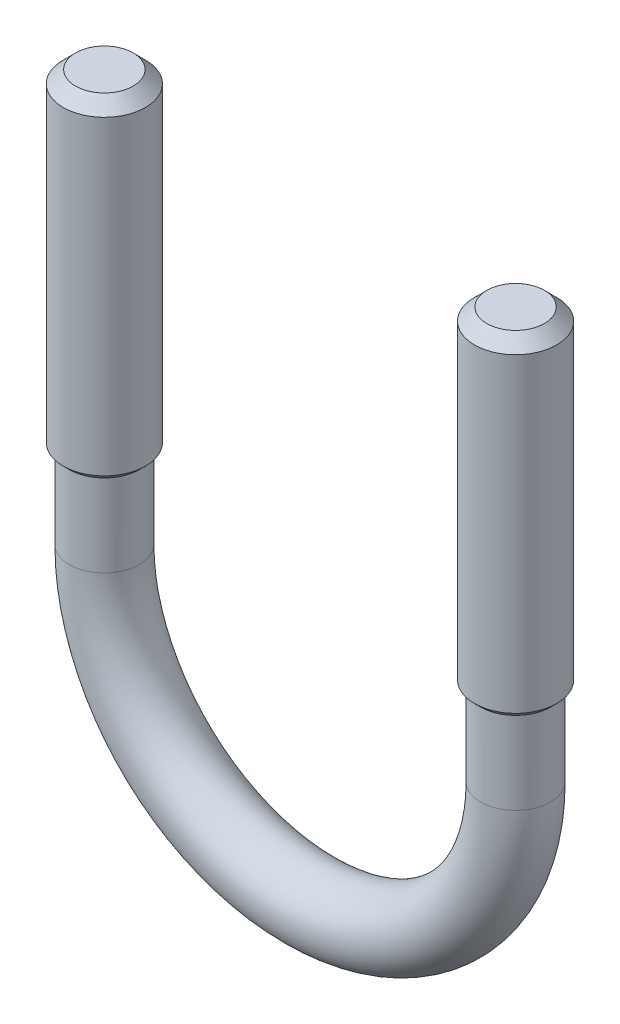
SolidWorks part; units mm, degrees
material "6061-T6 (SS)"
ref_plane "Front" through (0, 0, 0) normal (0, 0, 1) x (1, 0, 0)
ref_plane "Top" through (0, 0, 0) normal (0, 1, 0) x (1, 0, 0)
ref_plane "Right" through (0, 0, 0) normal (1, 0, 0) x (0, 0, -1)
sketch "Sketch1" plane through (0, 0, 0) normal (0, 0, 1) x (1, 0, 0)
  line L0 (-12.7, 31.75) -> (-19.05, 31.75) construction
  line L1 (-15.875, 31.75) -> (-15.875, 0) construction
  line L2 (0, -13.1699) -> (0, -18.5801)
  line L3 (15.875, 0) -> (15.875, 31.75) construction
  line L4 (19.05, 31.75) -> (12.7, 31.75) construction
  line L5 (-12.7, 6.35) -> (-19.05, 6.35)
  line L6 (0, -12.7) -> (0, -19.05) construction
  line L7 (-12.7, 31.75) -> (-12.7, 6.35)
  line L8 (-12.5625, 32.9406) -> (-12.5625, 31.6706) construction
  line L9 (-12.5625, 31.6706) -> (-13.6624, 32.3056) construction
  line L10 (-13.6624, 32.3056) -> (-12.5625, 32.9406) construction
  line L11 (-12.5625, 32.3056) -> (-12.7, 32.3056) construction
  line L12 (-13.6624, 32.3056) -> (-13.5249, 32.3056) construction
  line L13 (-12.7, 32.8612) -> (-12.7, 31.75) construction
  line L14 (-13.5249, 32.385) -> (-13.5249, 32.2262)
  line L15 (-12.6313, 32.9009) -> (-12.6313, 31.7103)
  line L16 (-12.6313, 31.7103) -> (-13.5249, 32.2262)
  line L17 (-13.5249, 32.385) -> (-12.6313, 32.9009)
  arc A0 (-15.875, 0) -> (15.875, 0) centre (0, 0) ccw construction
  circle A1 centre (0, 0) radius 12.7 construction
  point P5 (0, -15.875)
  point P8 (-15.875, 23.2833)
  point P15 (-15.875, 14.8167)
  point P18 (19.05, 29.21)
  point P21 (0, -15.875)
  point P31 (-12.7, 32.3056)
  point P34 (-13.5249, 32.3056)
  point P37 (-12.6313, 32.3056)
  dimension "ID" = 25.4
  dimension "Thread Size" = 6.35
  dimension "Thread Length" = 25.4
  dimension "Height" = 44.45
  dimension "D5" = 8.4667
  dimension "D6" = 8.4667
  dimension "Leg Diameter" = 5.4102
  dimension "D1" = 0.4699
  dimension "Center to Center" = 31.75
  dimension "D2" = 2.54
  dimension "Pitch" = 1.27
  dimension "D3" = 0.1588
ref_plane "Plane3" through (0, 31.75, 0) normal (0, 1, 0) x (-1, 0, 0)
sketch "Sketch2" plane through (0, 31.75, 0) normal (0, 1, 0) x (-1, 0, 0)
  circle A0 centre (15.875, 0) radius 3.175
extrude "Boss-Extrude1" add sketch "Sketch2" against normal up to vertex (25.4 mm away) up to point (-12.7, 6.35, 0)
sketch "Sketch6" [suppressed] plane through (0, 31.75, 0) normal (0, 1, 0) x (1, 0, 0)
  circle A1 centre (-15.875, 0) radius 3.175
  circle A2 centre (-15.875, 0) radius 3.175
  dimension "D1" = 0
chamfer "Chamfer2" distance 0.9525 angle 45 1 edges at (-15.875, 31.75, 3.175)
chamfer "Chamfer3" distance 0.4699 angle 45 1 edges at (-15.875, 6.35, 3.175)
mirror "Mirror2" about plane through (0, 0, 0) normal (1, 0, 0) of bodies 109
sketch "Sketch8" plane through (0, 0, 0) normal (0, 0, 1) x (1, 0, 0)
  line L0 (-15.875, 31.75) -> (-15.875, 0) construction
  line L1 (15.875, 0) -> (15.875, 31.75) construction
  line L2 (-15.875, 19.05) -> (-15.875, 0)
  line L3 (15.875, 0) -> (15.875, 19.05)
  line L5 (-12.7, 31.75) -> (-12.7, 6.35) construction
  arc A0 (-15.875, 0) -> (15.875, 0) centre (0, 0) ccw construction
  arc A1 (-15.875, 0) -> (15.875, 0) centre (0, 0) ccw
  point P16 (-12.7, 19.05)
sketch "Sketch12" plane through (0, 0, 0) normal (1, 0, 0) x (0, 0, -1)
  circle A0 centre (0, -15.875) radius 2.7051
sweep "Sweep1" add profiles "Sketch12" path "Sketch8"
ref_plane "Plane6" through (0, 23.2833, 0) normal (0, 1, 0) x (-1, 0, 0)
sketch "Sketch9" plane through (0, 23.2833, 0) normal (0, 1, 0) x (-1, 0, 0)
  line L0 (-19.05, 0) -> (-12.7, 0) construction
  line L1 (-19.0829, 5.5563) -> (-22.2908, 0)
  line L2 (-22.2908, 0) -> (-19.0829, -5.5563)
  line L3 (-19.0829, -5.5563) -> (-12.6671, -5.5563)
  line L4 (-12.6671, -5.5563) -> (-9.4592, 0)
  line L5 (-9.4592, 0) -> (-12.6671, 5.5563)
  line L6 (-12.6671, 5.5563) -> (-19.0829, 5.5563)
  circle A0 centre (-15.875, 0) radius 5.5562 construction
  circle A1 centre (-15.875, 0) radius 3.175
  circle A2 centre (15.875, 0) radius 3.175 construction
  dimension "Nut Size" = 11.1125
extrude "Boss-Extrude2" add sketch "Sketch9" along normal mid plane 5.5562 separate body
sketch "Sketch10" plane through (0, 26.0615, 0) normal (0, 1, 0) x (1, 0, 0)
  circle A0 centre (15.875, 0) radius 5.5562 construction
  circle A1 centre (15.875, 0) radius 5.5562
extrude "Cut-Extrude1" cut sketch "Sketch10" against normal through all draft 60 flip side to cut
sketch "Sketch11" plane through (0, 20.5052, 0) normal (0, -1, 0) x (1, 0, 0)
  circle A1 centre (15.875, 0) radius 5.5562
  circle A2 centre (15.875, 0) radius 5.5562
  dimension "D1" = 0
extrude "Cut-Extrude2" cut sketch "Sketch11" against normal through all draft 60 flip side to cut
chamfer "Chamfer4" distance 0.381 angle 45 2 edges at (15.875, 20.5052, 3.175) (15.875, 26.0615, 3.175)
pattern_linear "LPattern1" count 2 spacing 31.75 along (-1, 0, 0) of bodies 116
ref_plane "Plane5" [suppressed] through (0, 6.35, 0) normal (0, 1, 0) x (-1, 0, 0)
split "Split1" [suppressed] bodies to split 121
delete or keep bodies "Body-Delete/Keep 1" [suppressed] type delete bodies bodies 123 116
curve "Helix/Spiral1" [suppressed] pitch 1.27 height 26.67 turns 21 parameters "Pitch"=1.27
sketch "Sketch4" [suppressed] plane through (0, 0, 0) normal (0, 0, 1) x (1, 0, 0)
  line L0 (-13.5249, 32.385) -> (-12.6313, 32.9009) construction
  line L1 (-13.5249, 32.385) -> (-13.5249, 32.2262) construction
  line L2 (-12.6313, 31.7103) -> (-13.5249, 32.2262) construction
  line L3 (-12.6313, 32.9009) -> (-12.6313, 31.7103) construction
  line L4 (-13.5249, 32.385) -> (-13.5249, 32.2262)
  line L5 (-12.6313, 31.7103) -> (-13.5249, 32.2262)
  line L6 (-12.6313, 32.9009) -> (-12.6313, 31.7103)
  line L8 (-13.5249, 32.385) -> (-12.6313, 32.9009)
sweep "SweepCut1" [suppressed] cut profiles "Sketch4" path "Helix/Spiral1"
other "DeleteFace1" [suppressed]
other "Indent1" [suppressed] parameters "D1"=2.54, "D2"=0
pattern_linear "LPattern2" [suppressed] count 2 spacing 31.75 along (1, 0, 0) of bodies 110 127
combine bodies "Combine1" [suppressed] operation type add bodies to combine 110 125 128
delete or keep bodies "Body-Delete/Keep 2" type delete bodies bodies 116 122
equation "\"D3@Helix/Spiral1\"=\"Thread Length@Sketch1\" + \"Pitch@Sketch1\""
equation "\"D1@Chamfer2\" = \"Pitch@Sketch1\" * .75"
equation "\"D5@Sketch1\" = \"Thread Length@Sketch1\" / 3"
equation "\"D6@Sketch1\" = \"Thread Length@Sketch1\" / 3"
equation "\"D1@Chamfer3\"=\"D1@Sketch1\""
equation "\"D3@LPattern1\"=\"Center to Center@Sketch1\""
equation "\"D1@Chamfer4\"=\"Thread Size@Sketch1\"*.06"
equation "\"D3@LPattern2\"=\"Center to Center@Sketch1\""
equation "\"D3@Sketch1\"=\"Pitch@Sketch1\"/8"
equation "\"Pitch@Helix/Spiral1\"=\"Pitch@Sketch1\""
equation "\"D2@Sketch1\"=\"Pitch@Sketch1\"*2"
